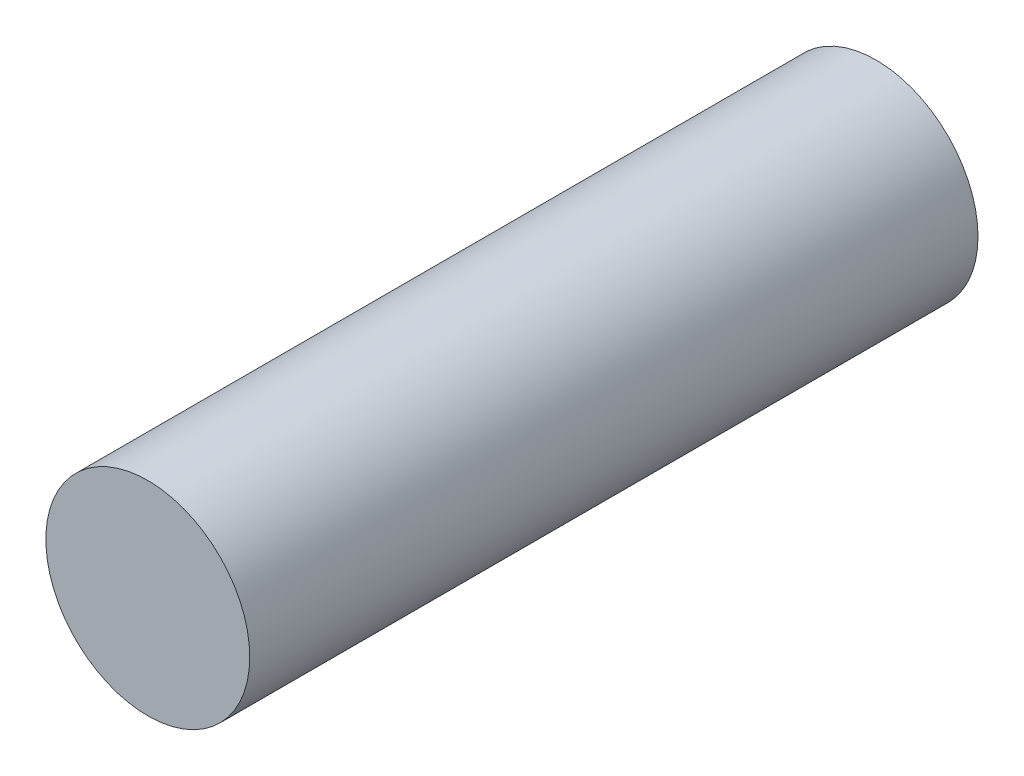
SolidWorks part; units mm, degrees
material "AISI 304"
ref_plane "Front Plane" through (0, 0, 0) normal (0, 0, 1) x (1, 0, 0)
ref_plane "Top Plane" through (0, 0, 0) normal (0, 1, 0) x (1, 0, 0)
ref_plane "Right Plane" through (0, 0, 0) normal (1, 0, 0) x (0, 0, -1)
sketch "Grip_Profile" plane through (0, 0, 0) normal (0, 0, 1) x (1, 0, 0)
  circle A0 centre (0, 0) radius 14
  dimension "Grip_Diameter" = 28
extrude "Grip_100mm" add sketch "Grip_Profile" along normal blind 100
ref_axis "Grip_Spin_Axis" through (0, 0, -5) along (0, 0, 1)
